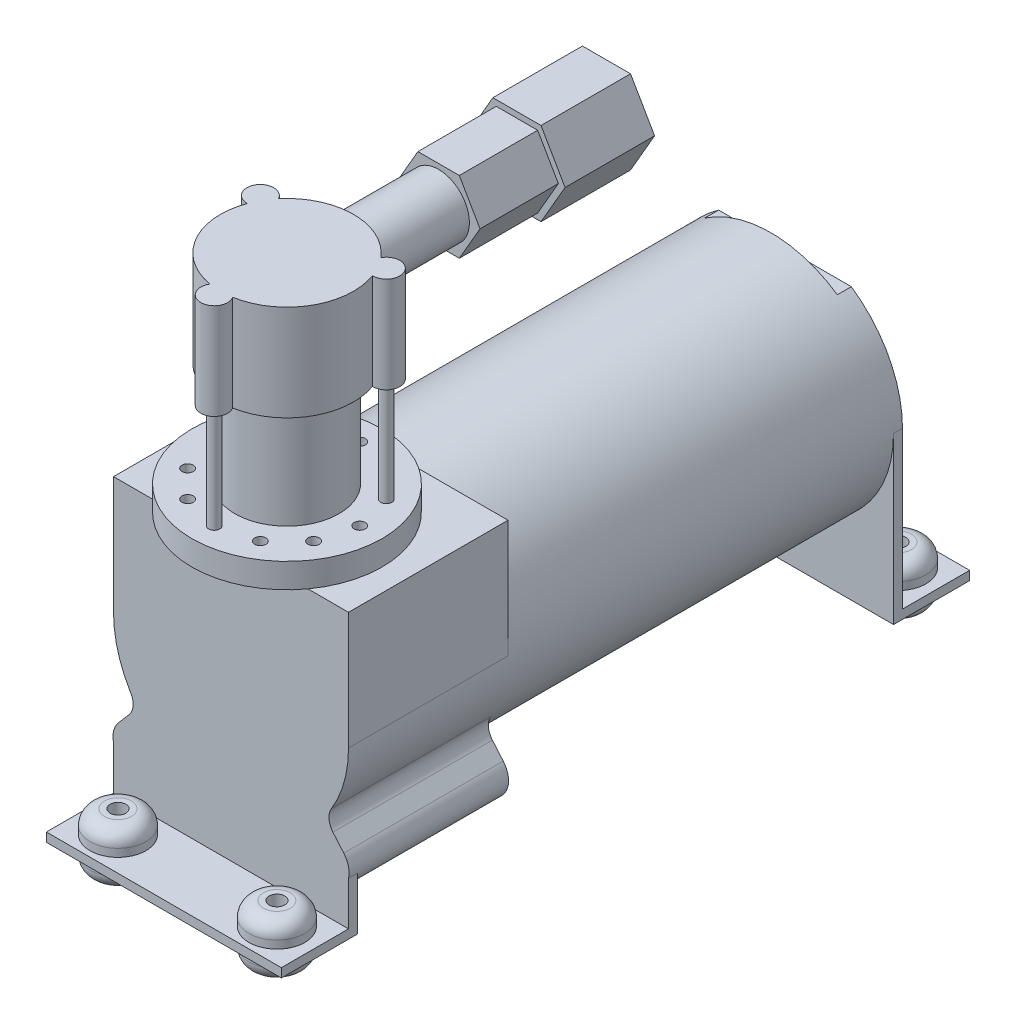
SolidWorks part; units mm, degrees
note: '?' marks a value the reader was unsure of.
ref_plane "Front Plane" through (0, 0, 0) normal (0, 0, 1) x (1, 0, 0)
ref_plane "Top Plane" through (0, 0, 0) normal (0, 1, 0) x (1, 0, 0)
ref_plane "Right Plane" through (0, 0, 0) normal (1, 0, 0) x (0, 0, -1)
sketch "Sketch1" plane through (0, 0, 0) normal (0, 0, 1) x (1, 0, 0)
  circle A0 centre (0, 0) radius 26.67
  dimension "D1" = 53.34
extrude "Boss-Extrude1" add sketch "Sketch1" along normal mid plane 125.73
sketch "Sketch2" plane through (0, 0, 62.865) normal (0, 0, 1) x (1, 0, 0)
  line L0 (0, 26.67) -> (0, -26.67) construction
  line L1 (0, 26.67) -> (26.67, 26.67)
  line L2 (26.67, 0) -> (26.67, 26.67)
  line L3 (15.4136, -25.1642) -> (17.9833, -27.9495)
  line L4 (23.1292, -18.3263) -> (25.5855, -21.2122)
  line L5 (26.797, -16.3536) -> (26.797, -28.4946) construction
  circle A0 centre (0, 0) radius 26.67 construction
  arc A1 (0, -26.67) -> (22.7767, -13.8748) centre (0, 0) ccw
  arc A2 (11.0366, -24.2792) -> (15.4136, -25.1642) centre (12.6133, -27.7477) cw
  arc A3 (17.9833, -27.9495) -> (25.5855, -21.2122) centre (21.717, -24.5048) ccw
  arc A4 (23.1292, -18.3263) -> (22.7767, -13.8748) centre (26.0306, -15.8569) cw
  arc A5 (26.67, 0) -> (0, 26.67) centre (0, 0) ccw
  circle M1 centre (0, 0) radius 26.67
  dimension "D3" = 3.81
  dimension "D4" = 5.08
  dimension "D1" = 26.797
  dimension "D2" = 15.687
  dimension "D5" = 3.7897
extrude "Boss-Extrude2" add sketch "Sketch2" against normal blind 36.195 contours L2 L1 M1 | L4 A4 A1 A2 L3 A3
mirror "Mirror1" about plane through (0, 0, 0) normal (1, 0, 0) of "Boss-Extrude2"
sketch "Sketch6" plane through (0, 0, -62.865) normal (0, 0, -1) x (-1, 0, 0)
  line L0 (-26.67, 0) -> (-26.67, -37.592)
  line L1 (-26.67, -37.592) -> (26.67, -37.592)
  line L2 (26.67, -37.592) -> (26.67, 0)
  circle A0 centre (0, 0) radius 26.67 construction
  arc A1 (-26.67, 0) -> (26.67, 0) centre (0, 0) ccw
  dimension "D1" = 37.592
extrude "Boss-Extrude4" add sketch "Sketch6" against normal blind 2.032
sketch "Sketch7" plane through (0, 0, -62.865) normal (0, 0, -1) x (-1, 0, 0)
  line L0 (26.67, -37.592) -> (26.67, 0) construction
  line L1 (-26.67, -37.592) -> (26.67, -37.592)
  line L2 (-26.67, -37.592) -> (-26.67, -35.56)
  line L3 (-26.67, -35.56) -> (26.67, -35.56)
  line L4 (26.67, -37.592) -> (26.67, -35.56)
  dimension "D1" = 2.032
extrude "Boss-Extrude5" add sketch "Sketch7" along normal blind 15.24
sketch "Sketch9" plane through (0, 0, 62.865) normal (0, 0, 1) x (1, 0, 0)
  line L3 (-17.9833, -27.9495) -> (-15.4136, -25.1642) construction
  line L4 (15.4136, -25.1642) -> (17.9833, -27.9495) construction
  line L7 (-26.67, 0) -> (-26.67, -37.592) construction
  line L8 (-26.67, -37.592) -> (26.67, -37.592) construction
  line L9 (26.67, -37.592) -> (26.67, 0) construction
  line L13 (-17.9833, -27.9495) -> (-15.4136, -25.1642)
  line L14 (15.4136, -25.1642) -> (17.9833, -27.9495)
  line L17 (-26.67, -25.6336) -> (-26.67, -37.592)
  line L18 (-26.67, -37.592) -> (26.67, -37.592)
  line L19 (26.67, -37.592) -> (26.67, -25.6336)
  arc A2 (-25.5855, -21.2122) -> (-17.9833, -27.9495) centre (-21.717, -24.5048) ccw construction
  arc A3 (-11.0366, -24.2792) -> (-15.4136, -25.1642) centre (-12.6133, -27.7477) ccw construction
  arc A4 (-11.0366, -24.2792) -> (11.0366, -24.2792) centre (0, 0) ccw construction
  arc A5 (15.4136, -25.1642) -> (11.0366, -24.2792) centre (12.6133, -27.7477) ccw construction
  arc A6 (17.9833, -27.9495) -> (25.5855, -21.2122) centre (21.717, -24.5048) ccw construction
  arc A9 (-26.67, 0) -> (26.67, 0) centre (0, 0) ccw construction
  arc A12 (-26.67, -25.6336) -> (-17.9833, -27.9495) centre (-21.717, -24.5048) ccw
  arc A13 (-11.0366, -24.2792) -> (-15.4136, -25.1642) centre (-12.6133, -27.7477) ccw
  arc A14 (-11.0366, -24.2792) -> (11.0366, -24.2792) centre (0, 0) ccw
  arc A15 (15.4136, -25.1642) -> (11.0366, -24.2792) centre (12.6133, -27.7477) ccw
  arc A16 (17.9833, -27.9495) -> (26.67, -25.6336) centre (21.717, -24.5048) ccw
  arc A19 (-11.0366, -24.2792) -> (11.0366, -24.2792) centre (0, 0) ccw
  arc M6 (-25.5855, -21.2122) -> (-17.9833, -27.9495) centre (-21.717, -24.5048) ccw
  line M7 (-17.9833, -27.9495) -> (-15.4136, -25.1642)
  arc M8 (-15.4136, -25.1642) -> (-11.0366, -24.2792) centre (-12.6133, -27.7477) cw
  arc M9 (-11.0366, -24.2792) -> (11.0366, -24.2792) centre (0, 0) ccw
  arc M10 (11.0366, -24.2792) -> (15.4136, -25.1642) centre (12.6133, -27.7477) cw
  line M11 (15.4136, -25.1642) -> (17.9833, -27.9495)
  arc M12 (17.9833, -27.9495) -> (25.5855, -21.2122) centre (21.717, -24.5048) ccw
extrude "Boss-Extrude6" add sketch "Sketch9" against normal blind 2.032 contours L18 L19 L17 M12 M11 M10 M9 M8 M7 M6
mirror "Mirror2" about plane through (0, 0, 0) normal (0, 0, 1) of "Boss-Extrude5"
sketch "Sketch10" plane through (0, 0, -62.865) normal (0, 0, -1) x (-1, 0, 0)
  line L0 (-15.0628, 22.0091) -> (15.0628, 22.0091)
  arc A2 (26.67, 0) -> (-26.67, 0) centre (0, 0) ccw construction
  arc A3 (15.0628, 22.0091) -> (-15.0628, 22.0091) centre (0, 0) ccw
  dimension "D1" = 4.6609
extrude "Cut-Extrude1" cut sketch "Sketch10" against normal blind 3.175
sketch "Sketch11" plane through (0, 0, -62.865) normal (0, 0, -1) x (-1, 0, 0)
  circle A0 centre (0, 0) radius 12.7
  dimension "D1" = 25.4
extrude "Boss-Extrude7" add sketch "Sketch11" along normal blind 3.302
sketch "Sketch12" plane through (0, -35.56, 0) normal (0, 1, 0) x (1, 0, 0)
  line L0 (-26.67, -70.485) -> (26.67, -70.485) construction
  line L1 (-26.67, -78.105) -> (-26.67, -62.865) construction
  line L2 (26.67, -78.105) -> (26.67, -62.865) construction
  line L3 (0, -62.865) -> (0, -78.105) construction
  line L4 (-26.67, -62.865) -> (26.67, -62.865) construction
  line L5 (-26.67, -78.105) -> (26.67, -78.105) construction
  circle A0 centre (-18.034, -70.485) radius 1.778
  circle A1 centre (18.034, -70.485) radius 1.778
  dimension "D2" = 3.556
  dimension "D1" = 36.068
extrude "Cut-Extrude2" cut sketch "Sketch12" against normal through all
ref_plane "Plane1" through (0, 0, 70.485) normal (0, 0, 1) x (1, 0, 0)
sketch "Sketch13" plane through (0, 0, 70.485) normal (0, 0, 1) x (1, 0, 0)
  line L0 (19.812, -35.56) -> (16.256, -35.56) construction
  line L1 (19.812, -35.56) -> (16.256, -35.56) construction
  line L2 (19.812, -35.56) -> (19.812, -30.48)
  line L3 (19.812, -30.48) -> (24.384, -30.48)
  line L4 (24.384, -30.48) -> (24.384, -35.56)
  line L5 (-26.67, -35.56) -> (26.67, -35.56) construction
  line L6 (24.384, -35.56) -> (19.812, -35.56)
  line L7 (18.034, -35.56) -> (18.034, -31.4302) construction
  line L8 (26.67, -36.576) -> (5.0172, -36.576) construction
  line L9 (26.67, -35.56) -> (26.67, -37.592) construction
  line L10 (19.812, -37.592) -> (16.256, -37.592) construction
  line L11 (24.384, -37.592) -> (19.812, -37.592)
  line L12 (24.384, -42.672) -> (24.384, -37.592)
  line L13 (19.812, -42.672) -> (24.384, -42.672)
  line L14 (19.812, -37.592) -> (19.812, -42.672)
  dimension "D1" = 12.7
  dimension "D2" = 5.08
revolve "Revolve1" add sketch "Sketch13" angle 360 about L7
mirror "Mirror3" about plane through (0, 0, 0) normal (1, 0, 0) of "Revolve1"
mirror "Mirror4" about plane through (0, 0, 0) normal (0, 0, 1) of "Mirror3", "Revolve1"
fillet "Fillet2" radius 3.302 8 edges at (18.034, -42.672, -64.135) (-18.034, -42.672, -64.135) (-18.034, -30.48, -64.135) (18.034, -30.48, -64.135) (-18.034, -42.672, 64.135) (18.034, -42.672, 64.135) (18.034, -30.48, 64.135) (-18.034, -30.48, 64.135)
sketch "Sketch14" plane through (0, 26.67, 0) normal (0, 1, 0) x (1, 0, 0)
  line L0 (-26.67, -78.105) -> (26.67, -78.105) construction
  circle A0 centre (0, -50.165) radius 11.811
  circle A1 centre (0, -50.165) radius 21.59
  dimension "D2" = 43.18
  dimension "D3" = 23.622
  dimension "D1" = 27.94
extrude "Boss-Extrude8" add sketch "Sketch14" along normal blind 5.588
sketch "Sketch15" plane through (0, 32.258, 0) normal (0, 1, 0) x (1, 0, 0)
  line L0 (0, -50.165) -> (0, -33.655) construction
  circle A0 centre (0, -50.165) radius 16.51 construction
  circle A3 centre (0, -33.655) radius 1.27
  dimension "D1" = 33.02
  dimension "D2" = 2.54
extrude "Cut-Extrude3" cut sketch "Sketch15" against normal up to surface (5.588 mm away) up to face at (0, 26.67, 67.31)
pattern_circular "CirPattern1" count 12 over 360 about axis through (0, 0, 50.165) along (0, 1, 0) of "Cut-Extrude3"
sketch "Sketch16" plane through (0, 26.67, 0) normal (0, 1, 0) x (1, 0, 0)
  circle A0 centre (0, -50.165) radius 11.811 construction
  circle A1 centre (0, -50.165) radius 11.811
  circle A2 centre (0, -66.675) radius 1.27 construction
  circle A3 centre (0, -66.675) radius 1.27
  circle A4 centre (-14.2981, -41.91) radius 1.27 construction
  circle A5 centre (14.2981, -41.91) radius 1.27 construction
  circle A6 centre (-14.2981, -41.91) radius 1.27
  circle A7 centre (14.2981, -41.91) radius 1.27
extrude "Boss-Extrude9" add sketch "Sketch16" along normal blind 29.21
sketch "Sketch18" plane through (0, 55.88, 0) normal (0, 1, 0) x (1, 0, 0)
  arc A1 (2.5823, -65.0558) -> (14.1869, -44.956) centre (0, -50.165) ccw
  circle A20 centre (14.2981, -41.91) radius 3.048
  arc A21 (14.1869, -44.956) -> (11.6046, -40.4833) centre (14.2981, -41.91) ccw
  circle A23 centre (-14.2981, -41.91) radius 3.048
  arc A24 (-11.6046, -40.4833) -> (-14.1869, -44.956) centre (-14.2981, -41.91) ccw
  arc A25 (-14.1869, -44.956) -> (-2.5823, -65.0558) centre (0, -50.165) ccw
  circle A26 centre (0, -66.675) radius 3.048
  arc A27 (-2.5823, -65.0558) -> (2.5823, -65.0558) centre (0, -66.675) ccw
  arc A28 (11.6046, -40.4833) -> (-11.6046, -40.4833) centre (0, -50.165) ccw
  dimension "D1" = 1.778
  dimension "D2" = 30.226
  dimension "D3" = 1.778
  dimension "D4" = 1.778
extrude "Boss-Extrude10" add sketch "Sketch18" along normal blind 21.7678
ref_plane "Plane2" through (0, 0, 35.052) normal (0, 0, -1) x (-1, 0, 0)
sketch "Sketch19" plane through (0, 0, 35.052) normal (0, 0, -1) x (-1, 0, 0)
  line L0 (-26.67, -37.592) -> (26.67, -37.592) construction
  circle A0 centre (0, 69.85) radius 6.985
  dimension "D2" = 13.97
  dimension "D1" = 107.442
extrude "Boss-Extrude11" add sketch "Sketch19" along normal blind 19.304 and the other way up to next (19.304 mm away)
sketch "Sketch20" plane through (0, 0, 15.748) normal (0, 0, -1) x (-1, 0, 0)
  line L1 (4.699, 61.7111) -> (9.398, 69.85)
  line L2 (9.398, 69.85) -> (4.699, 77.9889)
  line L3 (4.699, 77.9889) -> (-4.699, 77.9889)
  line L4 (-4.699, 77.9889) -> (-9.398, 69.85)
  line L5 (-9.398, 69.85) -> (-4.699, 61.7111)
  line L6 (-4.699, 61.7111) -> (4.699, 61.7111)
  circle A0 centre (0, 69.85) radius 8.1389 construction
  dimension "D1" = 9.398
extrude "Boss-Extrude12" add sketch "Sketch20" along normal blind 17.78
sketch "Sketch23" plane through (0, 0, -2.032) normal (0, 0, -1) x (-1, 0, 0)
  line L1 (10.922, 69.85) -> (5.461, 79.3087)
  line L2 (5.461, 79.3087) -> (-5.461, 79.3087)
  line L3 (-5.461, 79.3087) -> (-10.922, 69.85)
  line L4 (-10.922, 69.85) -> (-5.461, 60.3913)
  line L5 (-5.461, 60.3913) -> (5.461, 60.3913)
  line L6 (5.461, 60.3913) -> (10.922, 69.85)
  circle A0 centre (0, 69.85) radius 9.4587 construction
  circle A1 centre (0, 69.85) radius 5.715
  dimension "D2" = 11.43
  dimension "D1" = 10.922
extrude "Boss-Extrude15" add sketch "Sketch23" along normal blind 20.32
sketch "Sketch24" plane through (0, 0, -62.865) normal (0, 0, -1) x (-1, 0, 0)
  line L0 (-14.0001, 13.6857) -> (-22.8908, 13.6857) construction
  arc A0 (-15.0628, 22.0091) -> (-26.67, 0) centre (0, 0) ccw construction
  point P0 (-19.0801, 13.6857)
  point P1 (-14.0001, 13.6857)
  dimension "D1" = 5.08
  dimension "D2" = 8.8907
sketch "0_0_Point" plane through (0, 0, -62.865) normal (0, 0, -1) x (-1, 0, 0)
  point P0 (-19.0801, 13.6857)
other "0_0" parameters "Diameter"=2, "StubLength"=2
ref_axis "Axis1" through (19.0801, 13.6857, -72.865) along (0, 0, 1)?
sketch "1_0_Point" plane through (0, 0, -62.865) normal (0, 0, -1) x (-1, 0, 0)
  point P0 (-14.0001, 13.6857)
other "1_0" parameters "Diameter"=2, "StubLength"=2
ref_axis "Axis2" through (14.0001, 13.6857, -72.865) along (0, 0, 1)?
